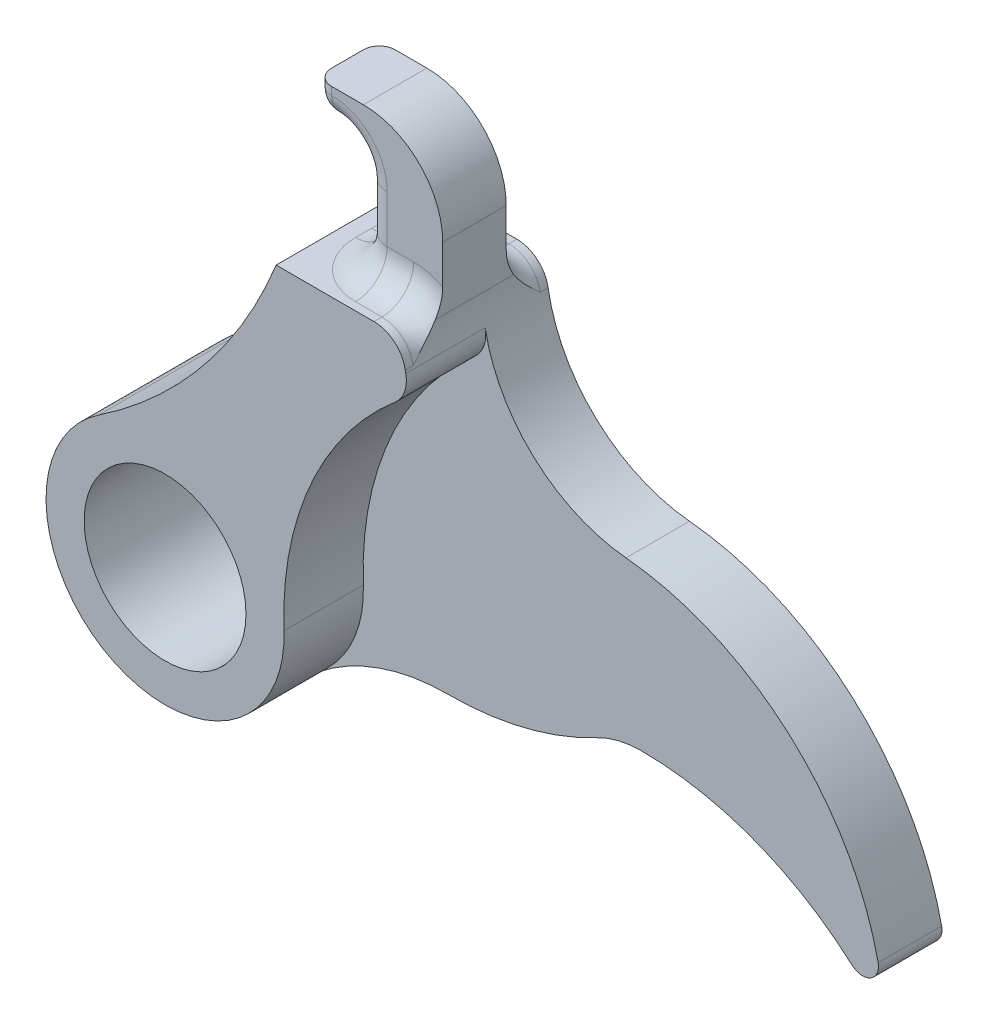
SolidWorks part; units mm, degrees
ref_plane "Спереди" through (0, 0, 0) normal (0, 0, 1) x (1, 0, 0)
ref_plane "Сверху" through (0, 0, 0) normal (0, 1, 0) x (1, 0, 0)
ref_plane "Справа" through (0, 0, 0) normal (1, 0, 0) x (0, 0, -1)
sketch "base" plane through (0, 0, 0) normal (0, 0, 1) x (1, 0, 0)
  line L0 (0, -25) -> (-25, -20) construction
  line L1 (0, 0) -> (9.5671, -23.097) construction
  line L2 (0, 0) -> (-9.5671, -23.097) construction
  line L3 (0, 0) -> (0, -25) construction
  line L4 (0, 0) -> (-2.4504, -24.8796) construction
  line L6 (0, 0) -> (-4.8773, -24.5196) construction
  line L7 (0, -25) -> (25, -20) construction
  line L11 (0, 0) -> (-7.2571, -23.9235) construction
  line L14 (0, 0) -> (7.2571, -23.9235) construction
  line L16 (0, 0) -> (4.8773, -24.5196) construction
  line L18 (0, 0) -> (2.4504, -24.8796) construction
  line L19 (-9.5671, -23.097) -> (9.5671, -23.097) construction
  arc A0 (-7.6537, -18.4776) -> (7.6537, -18.4776) centre (0, 0) ccw construction
  circle A1 centre (0, -25) radius 5 construction
  arc A6 (-9.5671, -23.097) -> (9.5671, -23.097) centre (0, 0) ccw construction
  point P12 (0, -20)
  dimension "D5" = 45
  dimension "D12" = 20
  dimension "ArmA" = 25
  dimension "ArmB" = 25.4951
  dimension "R" = 5
  dimension "base_offset" = 25
  dimension "stick_leverage" = 25
sketch "base-curve" plane through (0, 0, 0) normal (0, 0, 1) x (1, 0, 0)
  line L0 (0, -20) -> (0, -25) construction
  line L1 (0, 0) -> (-2.4504, -24.8796) construction
  line L2 (0, 0) -> (2.4504, -24.8796) construction
  line L5 (-25, -20) -> (0, -20) construction
  line L6 (0, -20) -> (25, -20) construction
  line L7 (10, -20) -> (10, 0) construction
  line L8 (-10, -20) -> (-10, 0) construction
  line L9 (-10, 0) -> (10, 0) construction
  line L10 (-25, -20) -> (-10, 0) construction
  line L11 (10, 0) -> (25, -20) construction
  line L13 (0, 0) -> (-4.8773, -24.5196) construction
  line L14 (0, 0) -> (4.8773, -24.5196) construction
  line L15 (0, 0) -> (-7.2571, -23.9235) construction
  line L16 (0, 0) -> (-9.5671, -23.097) construction
  line L17 (-2.2605, -20.5401) -> (-4.3096, -21.5787)
  line L18 (-4.3096, -21.5787) -> (-6.5058, -22.3844)
  line L19 (-6.5058, -22.3844) -> (-9.5586, -23.0612)
  line L20 (-9.5586, -23.0612) -> (-12.1501, -23.2901)
  line L21 (-2.5877, -26.2729) -> (-4.3096, -21.5787) construction
  line L22 (-8.4763, -27.9427) -> (-9.5586, -23.0612) construction
  line L23 (-5.4235, -27.2658) -> (-6.5058, -22.3844) construction
  line L24 (-11.7101, -28.2707) -> (-12.1501, -23.2901) construction
  line L25 (-22.6762, -27.1309) -> (-1.5492, -20.2461) construction
  line L26 (0, 0) -> (7.2571, -23.9235) construction
  line L27 (0, 0) -> (9.5671, -23.097) construction
  circle A0 centre (0, -25) radius 5 construction
  circle A1 centre (2.6465, -26.87) radius 5 construction
  circle A2 centre (-2.5877, -26.2729) radius 5 construction
  circle A4 centre (-5.4235, -27.2658) radius 5 construction
  circle A5 centre (-8.4763, -27.9427) radius 5 construction
  circle A6 centre (-25, -20) radius 7.5 construction
  circle A7 centre (-11.7101, -28.2707) radius 5 construction
  circle A8 centre (5.6576, -28.4428) radius 5 construction
  circle A9 centre (8.9988, -29.6652) radius 5 construction
  circle A10 centre (12.6286, -30.488) radius 5 construction
  point P3 (2.4504, -24.8796)
  point P11 (2.6465, -26.87)
  point P24 (-2.4504, -24.8796)
  point P25 (4.8773, -24.5196)
  point P27 (-4.8773, -24.5196)
  point P33 (-7.2571, -23.9235)
  point P36 (-9.5671, -23.097)
  point P39 (-2.5877, -26.2729)
  point P40 (5.6576, -28.4428)
  point P41 (-5.4235, -27.2658)
  point P42 (-8.4763, -27.9427)
  point P43 (-11.7101, -28.2707)
  point P64 (7.2571, -23.9235)
  point P65 (8.9988, -29.6652)
  point P68 (9.5671, -23.097)
  point P69 (12.6286, -30.488)
  dimension "D2" = 2
  dimension "D5" = 4.2
  dimension "D6" = 5.6
  dimension "D7" = 4
  dimension "D8" = 6
  dimension "D13" = 15
  dimension "D4" = 2.8
  dimension "D3" = 1.4
  dimension "D9" = 8
  dimension "spring" = 20
  dimension "b_long" = 53.13
  dimension "b_short" = 53.13
sketch "Эскиз2" plane through (0, 0, 0) normal (0, 0, 1) x (1, 0, 0)
  line L0 (-11.7101, -28.2707) -> (-12.1749, -23.0095) construction
  line L1 (-10, 0) -> (-18, 0) construction
  line L3 (-2.2605, -20.5401) -> (-4.3096, -21.5787) construction
  line L4 (0, -25) -> (0, 0) construction
  line L10 (-4.3096, -21.5787) -> (-6.5058, -22.3844) construction
  line L11 (-22.6602, -27.1257) -> (-1.8719, -20.2995) construction
  line L12 (-6.5058, -22.3844) -> (-9.5586, -23.0612) construction
  line L13 (-9.5586, -23.0612) -> (-12.1501, -23.2901) construction
  line L14 (-2.2605, -20.5401) -> (-4.3096, -21.5787) construction
  line L15 (-4.3096, -21.5787) -> (-6.5058, -22.3844) construction
  line L16 (-6.5058, -22.3844) -> (-9.5586, -23.0612) construction
  line L17 (-9.5586, -23.0612) -> (-12.1501, -23.2901) construction
  line L19 (0, -25) -> (0, -40) construction
  line L20 (0, -40) -> (15.3209, -27.1442) construction
  line L21 (-18, 0) -> (-15, 0)
  line L23 (-10, 0) -> (-10, 7)
  line L24 (-10, 7) -> (-15, 7)
  line L25 (-15, 0) -> (-15, 7)
  circle A0 centre (-25, -20) radius 7.5 construction
  arc A1 (-2.8021, -20.6945) -> (-12.1749, -23.0095) centre (-12.1425, -3.0096) cw
  arc A2 (-29.1682, -13.7649) -> (-20.3156, -25.8571) centre (-25, -20) ccw
  arc A3 (15.3209, -27.1442) -> (0, -20) centre (0, -40) ccw
  arc A5 (-29.1682, -13.7649) -> (-18, 0) centre (-45.8408, 11.1755) ccw
  arc A6 (-7.6537, -18.4776) -> (7.6537, -18.4776) centre (0, 0) ccw construction
  arc A7 (-9.5671, -23.097) -> (9.5671, -23.097) centre (0, 0) ccw construction
  arc A8 (-2.8021, -20.6945) -> (0, -20) centre (0, -26) cw
  arc A10 (15.3209, -27.1442) -> (-0.9516, -9.9546) centre (-2.6644, -27.8729) ccw
  arc A11 (-0.9516, -9.9546) -> (-10, 0) centre (0, 0) cw
  arc A13 (-16.899, -23.8901) -> (-9.55, -2.9661) centre (2.4797, -18.9437) cw construction
  arc A17 (-20.3156, -25.8571) -> (-12.1749, -23.0095) centre (-12.1959, -36.0095) cw
  point P48 (-2.5877, -26.2729)
  point P52 (-5.4235, -27.2658)
  point P54 (-8.4763, -27.9427)
  point P56 (-11.7101, -28.2707)
  dimension "D2" = 6
  dimension "D3" = 5
  dimension "D4" = 3
  dimension "D5" = 30
  dimension "D6" = 50
  dimension "D8" = 18
  dimension "80" = 20
  dimension "D9" = 20
  dimension "D10" = 20
  dimension "D11" = 7
  dimension "D14" = 13
  dimension "D7" = 10
  dimension "D1" = 8
extrude "Бобышка-Вытянуть1" add sketch "Эскиз2" along normal blind 9
sketch "Эскиз6" plane through (0, 0, 9) normal (0, 0, 1) x (1, 0, 0)
  arc A0 (-9.55, -2.9661) -> (-16.899, -23.8901) centre (2.4797, -18.9437) ccw construction
  arc A1 (-9.55, -2.9661) -> (-16.899, -23.8901) centre (2.4797, -18.9437) ccw
  arc A2 (15.3209, -27.1442) -> (-0.9516, -9.9546) centre (-2.6644, -27.8729) ccw construction
  arc A3 (-12.1749, -23.0095) -> (-20.3156, -25.8571) centre (-12.1959, -36.0095) ccw construction
  arc A4 (15.3209, -27.1442) -> (0, -20) centre (0, -40) ccw construction
  arc A5 (-10, 0) -> (-0.9516, -9.9546) centre (0, 0) ccw construction
  arc A6 (15.3209, -27.1442) -> (-0.9516, -9.9546) centre (-2.6644, -27.8729) ccw
  arc A7 (-9.55, -2.9661) -> (-0.9516, -9.9546) centre (0, 0) ccw
  arc A8 (15.3209, -27.1442) -> (0, -20) centre (0, -40) ccw
  arc A9 (-12.1749, -23.0095) -> (-2.8021, -20.6945) centre (-12.1425, -3.0096) ccw construction
  arc A10 (0, -20) -> (-2.8021, -20.6945) centre (0, -26) ccw construction
  arc A11 (-12.1749, -23.0095) -> (-16.899, -23.8901) centre (-12.1959, -36.0095) ccw
  arc A12 (-12.1749, -23.0095) -> (-2.8021, -20.6945) centre (-12.1425, -3.0096) ccw
  arc A13 (0, -20) -> (-2.8021, -20.6945) centre (0, -26) ccw
extrude "Вырез-Вытянуть1" cut sketch "Эскиз6" against normal blind 5
sketch "Эскиз12" plane through (-15, 0, 0) normal (-1, 0, 0) x (0, 0, 1)
  line L0 (9, 0) -> (0, 0) construction
  line L1 (0, 7) -> (2.5, 7)
  line L2 (0, 7) -> (0, 0)
  line L3 (0, 0) -> (2.5, 0)
  line L4 (2.5, 7) -> (2.5, 0)
  line L5 (4.5, 0) -> (4.5, 7) construction
  line L6 (9, 7) -> (0, 7) construction
  line L7 (6.5, 7) -> (6.5, 0)
  line L8 (9, 0) -> (6.5, 0)
  line L9 (9, 7) -> (9, 0)
  line L10 (9, 7) -> (6.5, 7)
  dimension "D1" = 4
extrude "Вырез-Вытянуть3" cut sketch "Эскиз12" against normal through all
fillet "Скругление11" radius 2 2 edges at (-10, 0, 1.25) (-10, 0, 7.75)
fillet "Скругление1" radius 1 1 edges at (15.3209, -27.1442, 2)
sketch "Эскиз10" plane through (0, 7, 0) normal (0, 1, 0) x (-1, 0, 0)
  line L0 (10, 6.5) -> (15, 6.5) construction
  line L1 (10, 2.5) -> (18, 2.5)
  line L2 (10, 2.5) -> (10, 6.5)
  line L3 (10, 6.5) -> (18, 6.5)
  line L4 (18, 2.5) -> (18, 6.5)
  line L5 (10, 6.5) -> (10, 2.5) construction
  line L6 (15, 6.5) -> (15, 2.5) construction
  dimension "D1" = 3
extrude "Бобышка-Вытянуть3" add sketch "Эскиз10" along normal blind 2
fillet "Скругление5" radius 5 1 edges at (-10, 9, 4.5)
fillet "Скругление10" radius 7.5 1 edges at (-16.899, -23.8901, 6.5)
fillet "Скругление14" radius 2 1 edges
fillet "Скругление15" radius 1.5 6 edges at (-15.5858, 6.4142, 2.5) (-15.5858, 6.4142, 6.5)
fillet "Скругление16" radius 2 7 edges at (-10.5412, -0.4725, 6.5) (-12.6661, 0, 6.5) (-10.5412, -0.4725, 2.5) (-12.6661, 0, 2.5) (-14.5607, 0, 2.9393) (-15, 0, 4.5) (-14.5607, 0, 6.0607)
fillet "Скругление17" radius 1 5 edges at (-18, 8.75, 2.5) (-18, 7.4393, 2.9393) (-18, 7, 4.5) (-18, 8.75, 6.5) (-18, 7.4393, 6.0607)
fillet "Скругление18" radius 2 1 edges at (-9.55, -2.9661, 6.5)
sketch "Эскиз11" plane through (0, 0, 9) normal (0, 0, 1) x (1, 0, 0)
  circle A0 centre (-25, -20) radius 5 construction
  arc A1 (-29.1682, -13.7649) -> (-20.3156, -25.8571) centre (-25, -20) ccw construction
  circle A2 centre (-25, -20) radius 5.1
  dimension "D1" = 10
  dimension "tolerance" = 0.1
extrude "Вырез-Вытянуть2" cut sketch "Эскиз11" against normal through all
equation "\"rad\"= 0.0174533"
equation "\"radius_offset\"= 10"
equation "\"spring_power\"= 200'g"
equation "\"D4@base-curve\"=\"D3@base-curve\"*2"
equation "\"D5@base-curve\"=\"D3@base-curve\"*3"
equation "\"D6@base-curve\"=\"D3@base-curve\"*4"
equation "\"D7@base-curve\"=\"D2@base-curve\"*2"
equation "\"D8@base-curve\"=\"D2@base-curve\"*3"
equation "\"D9@base-curve\"=\"D2@base-curve\"*4"
